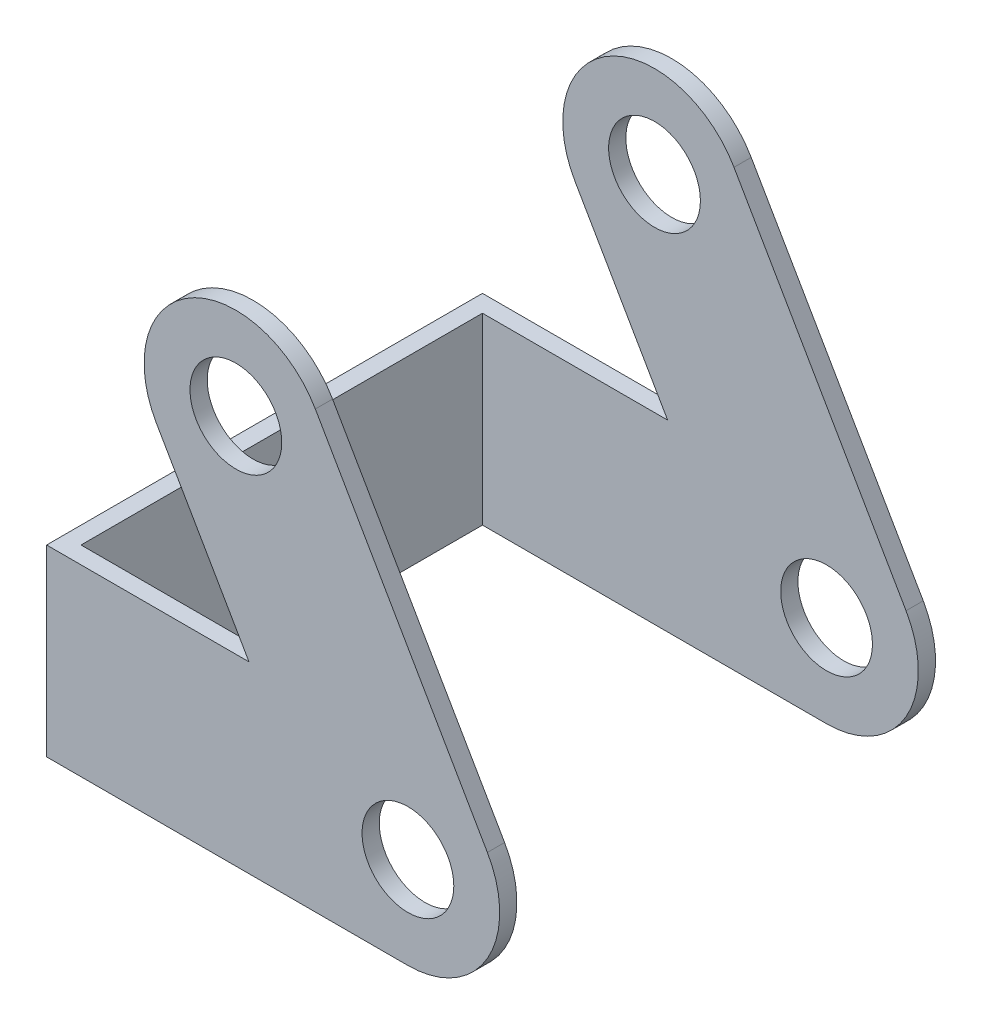
SolidWorks part; units mm, degrees
ref_plane "Front Plane" through (0, 0, 0) normal (0, 0, 1) x (1, 0, 0)
ref_plane "Top Plane" through (0, 0, 0) normal (0, 1, 0) x (1, 0, 0)
ref_plane "Right Plane" through (0, 0, 0) normal (1, 0, 0) x (0, 0, -1)
sketch "Sketch1" plane through (0, 0, 0) normal (0, 0, 1) x (1, 0, 0)
  line L0 (-16.1436, 59.9615) -> (13.8564, 8)
  line L1 (-43.8564, 43.9615) -> (-27.7128, 16)
  line L2 (0, -16) -> (-60, -16)
  line L3 (-60, -16) -> (-60, 16)
  line L4 (-60, 16) -> (-27.7128, 16)
  line L5 (-16.1436, 59.9615) -> (-43.8564, 43.9615) construction
  line L6 (0, 0) -> (-30, 51.9615) construction
  circle A0 centre (0, 0) radius 8
  circle A1 centre (-30, 51.9615) radius 8
  arc A2 (0, -16) -> (13.8564, 8) centre (0, 0) ccw
  arc A4 (-43.8564, 43.9615) -> (-16.1436, 59.9615) centre (-30, 51.9615) cw
  dimension "D1" = 60
  dimension "D2" = 16
  dimension "D3" = 32
  dimension "D4" = 60
  dimension "D5" = 60
extrude "Boss-Extrude1" add sketch "Sketch1" along normal blind 3 contours A4 L1 L4 L3 L2 A2 L0 A1 A0 region at (-23.639, 15.9787, 0)
sketch "Sketch2" plane through (-60, 0, 0) normal (-1, 0, 0) x (0, 0, 1)
  line L0 (3, -16) -> (0, -16) construction
  line L1 (3, 16) -> (-73, 16)
  line L2 (3, 16) -> (3, -16)
  line L3 (3, -16) -> (-73, -16)
  line L4 (-73, 16) -> (-73, -16)
  line L5 (3, 16) -> (0, 16) construction
  point P7 (0, 0)
  point P8 (0, 0)
  dimension "D1" = 76
extrude "Boss-Extrude2" add sketch "Sketch2" along normal blind 3
extrude "Boss-Extrude3" add sketch "Sketch1<2>" along normal blind 3 from surface contours A4 L1 L4 L3 L2 A2 L0 A1 A0 region at (-23.639, 15.9787, 0) starting at face at (-61.5, 0, -73)
sketch "Sketch1<2>" plane through (0, 0, 0) normal (0, 0, 1) x (1, 0, 0) same geometry as "Sketch1"
